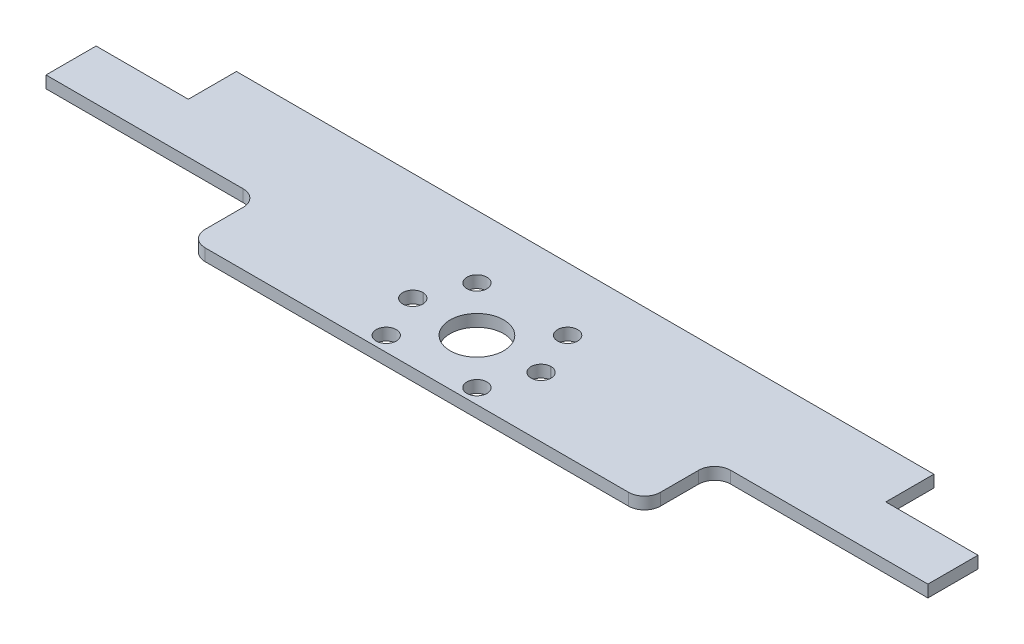
SolidWorks part; units mm, degrees
ref_plane "前视基准面" through (0, 0, 0) normal (0, 0, 1) x (1, 0, 0)
ref_plane "上视基准面" through (0, 0, 0) normal (0, 1, 0) x (1, 0, 0)
ref_plane "右视基准面" through (0, 0, 0) normal (1, 0, 0) x (0, 0, -1)
other "Configuration Table"
sketch "草图2" plane through (0, 0, 0) normal (0, 1, 0) x (1, 0, 0)
  line L0 (110, -9.2483) -> (-110, -9.2483)
  line L1 (110, -26.7483) -> (-110, -26.7483)
  line L2 (110, -26.7483) -> (110, 15.2517)
  line L3 (110, 15.2517) -> (-110, 15.2517)
  line L4 (-110, -26.7483) -> (-110, 15.2517)
  line L6 (-110, 3.2517) -> (-87, 3.2517)
  line L7 (56.8055, -9.2483) -> (56.8055, -26.7483)
  line L8 (0, -9.2483) -> (0, 15.2517)
  line L9 (-56.8055, -9.2483) -> (-56.8055, -26.7483)
  line L10 (-87, 3.2517) -> (-87, 15.2517)
  line L11 (87, 3.2517) -> (87, 15.2517)
  line L12 (110, 3.2517) -> (87, 3.2517)
  circle A0 centre (0, -11.7483) radius 6.682
  circle A1 centre (11.3137, -0.4346) radius 2.5
  circle A2 centre (0, -11.7483) radius 16
  circle A3 centre (16, -11.7483) radius 2.5
  circle A4 centre (11.3137, -23.062) radius 2.5
  circle A5 centre (0, -27.7483) radius 2.5
  circle A6 centre (-11.3137, -23.062) radius 2.5
  circle A7 centre (-16, -11.7483) radius 2.5
  circle A8 centre (-11.3137, -0.4346) radius 2.5
  circle A9 centre (0, 4.2517) radius 2.5
  point P0 (0, 0)
  point P20 (0, 0)
  point P37 (0, -11.7483)
  point P42 (0, 0)
  point P43 (0, 0)
  dimension "D3" = 5
  dimension "D1" = 220
  dimension "D2" = 17.5
  dimension "D5" = 42
  dimension "D7" = 23
  dimension "D8" = 12
  dimension "D4" = 8
extrude "凸台-拉伸1" add sketch "草图2" along normal blind 3 contours A7 A2 A6 L1 A5 A4 A3 L0 A0 | A9 L8 A0 L0 A2 A1 | A9 A2 A8 L0 A0 L8 | A9 L8 L3 L4 L0 A2 A8 | A9 A2 A1 L0 L2 L3 L8 | L1 A5 | A4 A2 L1 L7 L0 A3 | A7 L0 L9 L1 A2 A6 | A9 region at (53.4494, 0, -2.7134) region at (35.6553, 0, 18.309) region at (15.4472, 0, 9.3085) region at (6.9935, 0, 3.4384) region at (0, 0, 26.1296) region at (-53.4494, 0, -2.7134) region at (-6.9935, 0, 3.4384) region at (-35.6553, 0, 18.309)
fillet "圆角1" radius 4 4 edges at (56.8055, 1.5, 9.2483) (56.8055, 1.5, 26.7483) (-56.8055, 1.5, 9.2483) (-56.8055, 1.5, 26.7483)
